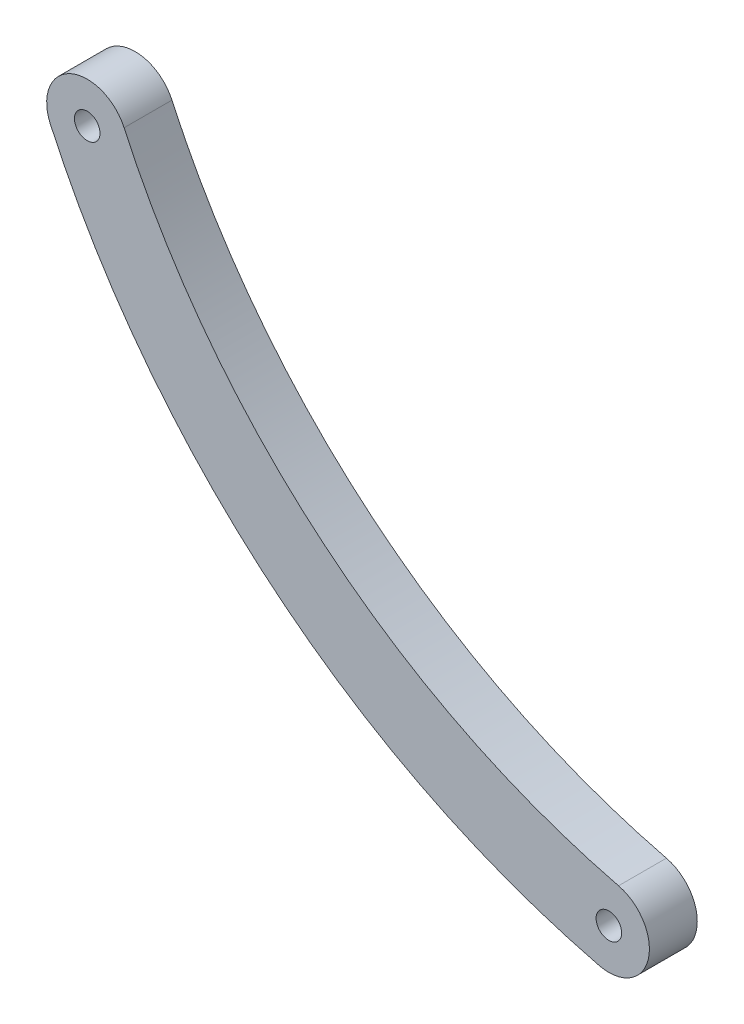
SolidWorks part; units mm, degrees
ref_plane "Front Plane" through (0, 0, 0) normal (0, 0, 1) x (1, 0, 0)
ref_plane "Top Plane" through (0, 0, 0) normal (0, 1, 0) x (1, 0, 0)
ref_plane "Right Plane" through (0, 0, 0) normal (1, 0, 0) x (0, 0, -1)
sketch "Sketch1" plane through (0, 0, 0) normal (0, 0, 1) x (1, 0, 0)
  circle A0 centre (219.0801, 113.733) radius 1.6
  arc A2 (149.1069, 165.7123) -> (217.8668, 108.8001) centre (242.3622, 208.3879) ccw
  arc A3 (158.3455, 169.94) -> (220.2935, 118.666) centre (242.3622, 208.3879) ccw
  arc A4 (158.3455, 169.94) -> (149.1069, 165.7123) centre (153.7262, 167.8261) ccw
  arc A5 (217.8668, 108.8001) -> (220.2935, 118.666) centre (219.0801, 113.733) ccw
  circle A8 centre (153.7262, 167.8261) radius 1.6
extrude "Boss-Extrude1" add sketch "Sketch1" along normal blind 5.9944
